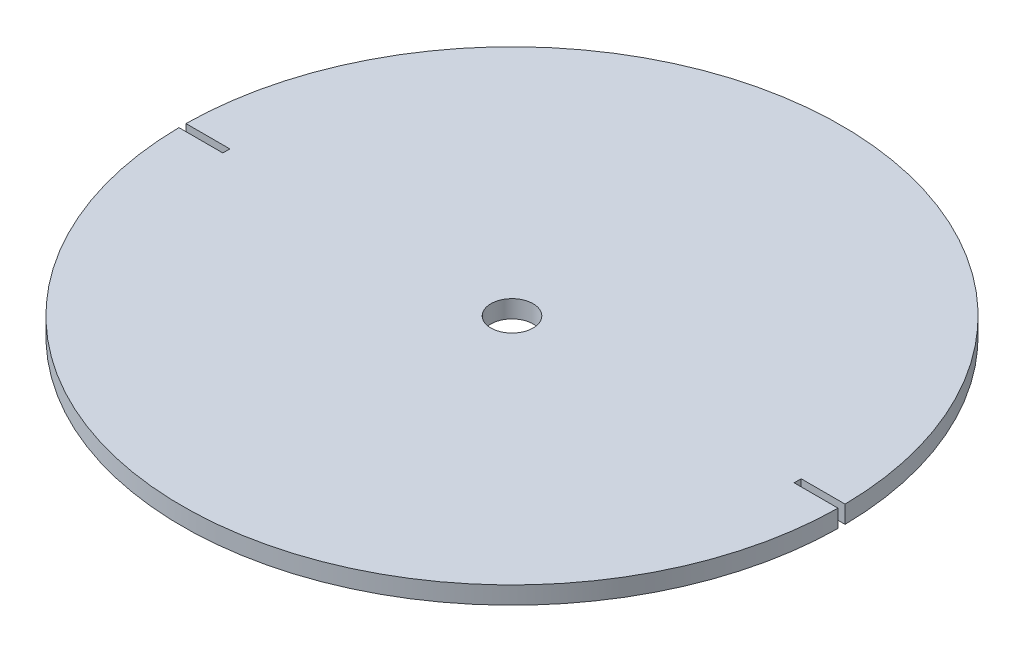
SolidWorks part; units mm, degrees
ref_plane "정면" through (0, 0, 0) normal (0, 0, 1) x (1, 0, 0)
ref_plane "윗면" through (0, 0, 0) normal (0, 1, 0) x (1, 0, 0)
ref_plane "우측면" through (0, 0, 0) normal (1, 0, 0) x (0, 0, -1)
sketch "스케치1" plane through (0, 0, 0) normal (0, 1, 0) x (1, 0, 0)
  line L9 (12.9797, -31.3358) -> (31.3358, -12.9797)
  line L10 (-5.9316, 14.3201) -> (-14.3201, 5.9316)
  line L11 (-14.3201, 5.9316) -> (-14.3201, -5.9316)
  line L12 (-14.3201, -5.9316) -> (-5.9316, -14.3201)
  line L13 (-5.9316, -14.3201) -> (5.9316, -14.3201)
  line L14 (5.9316, -14.3201) -> (14.3201, -5.9316)
  line L15 (14.3201, -5.9316) -> (14.3201, 5.9316)
  line L16 (14.3201, 5.9316) -> (5.9316, 14.3201)
  line L17 (5.9316, 14.3201) -> (-5.9316, 14.3201)
  line L18 (7.7493, -18.7086) -> (18.7086, -7.7493)
  line L19 (18.7086, -7.7493) -> (18.7086, 7.7493)
  line L20 (18.7086, 7.7493) -> (7.7493, 18.7086)
  line L21 (7.7493, 18.7086) -> (-7.7493, 18.7086)
  line L22 (-7.7493, 18.7086) -> (-18.7086, 7.7493)
  line L23 (-18.7086, 7.7493) -> (-18.7086, -7.7493)
  line L24 (-18.7086, -7.7493) -> (-7.7493, -18.7086)
  line L25 (-7.7493, -18.7086) -> (7.7493, -18.7086)
  line L26 (-9.7584, -23.5589) -> (9.7584, -23.5589)
  line L27 (9.7584, -23.5589) -> (23.5589, -9.7584)
  line L28 (23.5589, -9.7584) -> (23.5589, 9.7584)
  line L29 (23.5589, 9.7584) -> (9.7584, 23.5589)
  line L30 (9.7584, 23.5589) -> (-9.7584, 23.5589)
  line L31 (-9.7584, 23.5589) -> (-23.5589, 9.7584)
  line L32 (-23.5589, 9.7584) -> (-23.5589, -9.7584)
  line L33 (-23.5589, -9.7584) -> (-9.7584, -23.5589)
  line L34 (13.3939, -32.3358) -> (32.3358, -13.3939)
  line L35 (32.3358, -13.3939) -> (32.3358, 13.3939)
  line L36 (32.3358, 13.3939) -> (13.3939, 32.3358)
  line L37 (13.3939, 32.3358) -> (-13.3939, 32.3358)
  line L38 (-13.3939, 32.3358) -> (-32.3358, 13.3939)
  line L39 (-32.3358, 13.3939) -> (-32.3358, -13.3939)
  line L40 (-32.3358, -13.3939) -> (-13.3939, -32.3358)
  line L41 (-13.3939, -32.3358) -> (13.3939, -32.3358)
  line L42 (31.3358, -12.9797) -> (31.3358, 12.9797)
  line L43 (31.3358, 12.9797) -> (12.9797, 31.3358)
  line L44 (12.9797, 31.3358) -> (-12.9797, 31.3358)
  line L45 (-12.9797, 31.3358) -> (-31.3358, 12.9797)
  line L46 (-31.3358, 12.9797) -> (-31.3358, -12.9797)
  line L47 (-31.3358, -12.9797) -> (-12.9797, -31.3358)
  line L48 (-12.9797, -31.3358) -> (12.9797, -31.3358)
  line L49 (-9.3442, -22.5589) -> (9.3442, -22.5589)
  line L50 (9.3442, -22.5589) -> (22.5589, -9.3442)
  line L51 (22.5589, -9.3442) -> (22.5589, 9.3442)
  line L52 (22.5589, 9.3442) -> (9.3442, 22.5589)
  line L53 (9.3442, 22.5589) -> (-9.3442, 22.5589)
  line L54 (-9.3442, 22.5589) -> (-22.5589, 9.3442)
  line L55 (-22.5589, 9.3442) -> (-22.5589, -9.3442)
  line L56 (-22.5589, -9.3442) -> (-9.3442, -22.5589)
  line L57 (7.3351, -17.7086) -> (17.7086, -7.3351)
  line L58 (17.7086, -7.3351) -> (17.7086, 7.3351)
  line L59 (17.7086, 7.3351) -> (7.3351, 17.7086)
  line L60 (7.3351, 17.7086) -> (-7.3351, 17.7086)
  line L61 (-7.3351, 17.7086) -> (-17.7086, 7.3351)
  line L62 (-17.7086, 7.3351) -> (-17.7086, -7.3351)
  line L63 (-17.7086, -7.3351) -> (-7.3351, -17.7086)
  line L64 (-7.3351, -17.7086) -> (7.3351, -17.7086)
  line L65 (-5.5174, 13.3201) -> (-13.3201, 5.5174)
  line L66 (-13.3201, 5.5174) -> (-13.3201, -5.5174)
  line L67 (-13.3201, -5.5174) -> (-5.5174, -13.3201)
  line L68 (-5.5174, -13.3201) -> (5.5174, -13.3201)
  line L69 (5.5174, -13.3201) -> (13.3201, -5.5174)
  line L70 (13.3201, -5.5174) -> (13.3201, 5.5174)
  line L71 (13.3201, 5.5174) -> (5.5174, 13.3201)
  line L72 (5.5174, 13.3201) -> (-5.5174, 13.3201)
  line L81 (11.2576, -27.1783) -> (27.1783, -11.2576)
  line L82 (11.6718, -28.1783) -> (28.1783, -11.6718)
  line L83 (28.1783, -11.6718) -> (28.1783, 11.6718)
  line L84 (28.1783, 11.6718) -> (11.6718, 28.1783)
  line L85 (11.6718, 28.1783) -> (-11.6718, 28.1783)
  line L86 (-11.6718, 28.1783) -> (-28.1783, 11.6718)
  line L87 (-28.1783, 11.6718) -> (-28.1783, -11.6718)
  line L88 (-28.1783, -11.6718) -> (-11.6718, -28.1783)
  line L89 (-11.6718, -28.1783) -> (11.6718, -28.1783)
  line L90 (27.1783, -11.2576) -> (27.1783, 11.2576)
  line L91 (27.1783, 11.2576) -> (11.2576, 27.1783)
  line L92 (11.2576, 27.1783) -> (-11.2576, 27.1783)
  line L93 (-11.2576, 27.1783) -> (-27.1783, 11.2576)
  line L94 (-27.1783, 11.2576) -> (-27.1783, -11.2576)
  line L95 (-27.1783, -11.2576) -> (-11.2576, -27.1783)
  line L96 (-11.2576, -27.1783) -> (11.2576, -27.1783)
  circle A1 centre (0, 0) radius 15.5 construction
  circle A2 centre (0, 0) radius 20.25 construction
  circle A3 centre (0, 0) radius 25.5 construction
  circle A4 centre (0, 0) radius 35 construction
  circle A5 centre (0, 0) radius 30.5 construction
  dimension "D2" = 31
  dimension "D3" = 40.5
  dimension "D4" = 51
  dimension "D5" = 70
  dimension "D11" = 61
  dimension "D6" = 1
  dimension "D7" = 1
  dimension "D8" = 1
  dimension "D9" = 1
  dimension "D12" = 1
sketch "스케치3" plane through (0, 0, 0) normal (0, 1, 0) x (1, 0, 0)
  circle A1 centre (0, 0) radius 37.5
  dimension "D1" = 75
extrude "보스-돌출1" add sketch "스케치3" along normal blind 2
extrude "컷-돌출5" cut sketch "스케치1" along normal blind 1.2 contours L40 L41 L34 L35 L36 L37 L38 L39 L48 L47 L46 L45 L44 L43 L42 L9 | L32 L33 L26 L27 L28 L29 L30 L31 L56 L55 L54 L53 L52 L51 L50 L49 | L24 L25 L18 L19 L20 L21 L22 L23 L64 L63 L62 L61 L60 L59 L58 L57 | L16 L17 L10 L11 L12 L13 L14 L15 L72 L71 L70 L69 L68 L67 L66 L65 | L88 L89 L82 L83 L84 L85 L86 L87 L96 L95 L94 L93 L92 L91 L90 L81 region at (0, 0, -13.9151) region at (0, 0, 18.1794) region at (-16.1875, 0, 16.1875) region at (0, 0, 31.4212) region at (0, 0, 27.3813)
sketch "스케치4" plane through (0, 2, 0) normal (0, 1, 0) x (1, 0, 0)
  line L0 (-37.5, 0) -> (-32.5, 0) construction
  line L1 (-37.5, 0.4) -> (-32.5, 0.4)
  line L2 (-37.5, 0.4) -> (-37.5, -0.4)
  line L3 (-37.5, -0.4) -> (-32.5, -0.4)
  line L4 (-32.5, 0.4) -> (-32.5, -0.4)
  line L5 (0, -55) -> (0, 55) construction
  line L6 (-55, 0) -> (55, 0) construction
  line L7 (37.5, -0.4) -> (32.5, -0.4)
  line L8 (32.5, 0.4) -> (32.5, -0.4)
  line L9 (37.5, 0.4) -> (32.5, 0.4)
  line L10 (37.5, 0.4) -> (37.5, -0.4)
  dimension "D1" = 5
  dimension "D2" = 0.8
  dimension "D3" = 37.5
extrude "컷-돌출6" cut sketch "스케치4" against normal through all
sketch "스케치5" plane through (0, 2, 0) normal (0, 1, 0) x (1, 0, 0)
  circle A0 centre (0, 0) radius 2.4
  dimension "D1" = 4.8
extrude "컷-돌출7" cut sketch "스케치5" against normal through all
